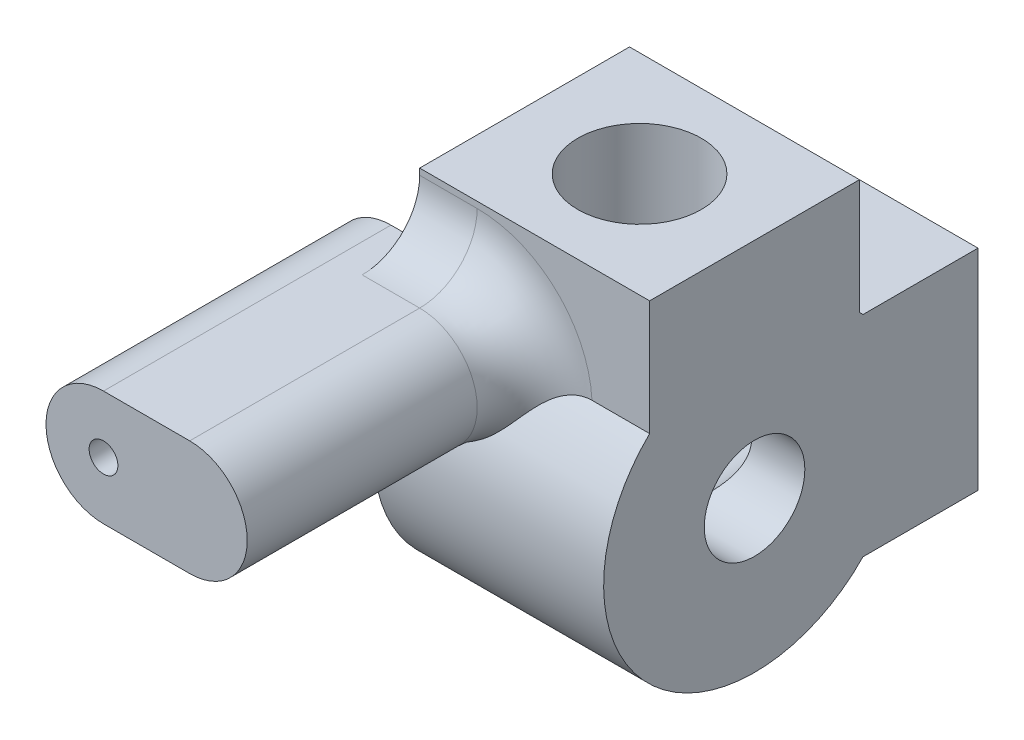
SolidWorks part; units mm, degrees
material "PLA Black"
ref_plane "Front" through (0, 0, 0) normal (0, 0, 1) x (1, 0, 0)
ref_plane "Top" through (0, 0, 0) normal (0, 1, 0) x (1, 0, 0)
ref_plane "Right" through (0, 0, 0) normal (1, 0, 0) x (0, 0, -1)
sketch "Sketch1" plane through (0, 0, 0) normal (1, 0, 0) x (0, 0, -1)
  line L0 (1.118, 1) -> (-1.118, 1) construction
  line L1 (-3.65, 3.7736) -> (3.65, 3.7736)
  line L2 (3.7736, 3.65) -> (3.7736, -3.65)
  line L3 (0, 0) -> (11.6334, 0) construction
  line L4 (0, 0) -> (0, 8.6732) construction
  arc A0 (-1.118, 1) -> (1.118, 1) centre (0, 0) ccw construction
  circle A1 centre (0, 0) radius 1.75
  arc A2 (3.7736, -3.65) -> (-3.65, 3.7736) centre (0, 0) cw
  arc A3 (3.7736, 3.65) -> (3.65, 3.7736) centre (0, 0) ccw
  dimension "D1" = 3
  dimension "D3" = 0.25
  dimension "D5" = 3.5
  dimension "D2" = 1
  dimension "D4" = 7.3
extrude "Boss-Extrude1" add sketch "Sketch1" along normal mid plane 8
sketch "Sketch2" plane through (0, 3.7736, 0) normal (0, 1, 0) x (1, 0, 0)
  circle A0 centre (0, 0) radius 2.15
  dimension "D1" = 4.3
extrude "Cut-Extrude1" cut sketch "Sketch2" against normal blind 5
sketch "Sketch3" plane through (0, 0, -3.7736) normal (0, 0, -1) x (-1, 0, 0)
  circle A0 centre (0, 0) radius 2.15
  dimension "D1" = 4.3
extrude "Cut-Extrude2" cut sketch "Sketch3" against normal blind 5
sketch "Sketch4" plane through (0, 3.7736, 0) normal (0, 1, 0) x (1, 0, 0)
  line L0 (4, 3.65) -> (-4, 3.65) construction
  line L1 (4, 3.65) -> (4, -3.65) construction
  line L2 (4, -3.65) -> (-4, -3.65) construction
  line L3 (-4, 3.65) -> (-4, -3.65) construction
  line L4 (4, 3.65) -> (-4, 3.65)
  line L5 (4, 3.65) -> (4, -3.65)
  line L6 (4, -3.65) -> (-4, -3.65)
  line L7 (-4, 3.65) -> (-4, -3.65)
  circle A0 centre (0, 0) radius 2.15 construction
  circle A1 centre (0, 0) radius 2.15
extrude "Boss-Extrude2" add sketch "Sketch4" along normal blind 4
sketch "Sketch5" plane through (0, 0, -3.7736) normal (0, 0, -1) x (-1, 0, 0)
  line L0 (-4, 3.65) -> (4, 3.65) construction
  line L1 (4, -3.65) -> (4, 3.65) construction
  line L2 (-4, -3.65) -> (4, -3.65) construction
  line L3 (-4, -3.65) -> (-4, 3.65) construction
  line L4 (-4, 3.65) -> (4, 3.65)
  line L5 (4, -3.65) -> (4, 3.65)
  line L6 (-4, -3.65) -> (4, -3.65)
  line L7 (-4, -3.65) -> (-4, 3.65)
  circle A0 centre (0, 0) radius 2.15 construction
  circle A1 centre (0, 0) radius 2.15
extrude "Boss-Extrude3" add sketch "Sketch5" along normal blind 4
ref_axis "Axis1" through (4, 0, 0) along (-1, 0, 0)
sketch "Sketch6" plane through (0, 0, 3.65) normal (0, 0, 1) x (1, 0, 0)
  line L0 (-4, 7.7736) -> (-4, 3.7736) construction
  line L2 (-2, 5.555) -> (-5, 5.555)
  line L3 (-5, 1.555) -> (-2, 1.555)
  line L6 (4, 0) -> (-4, 0) construction
  circle A0 centre (-5, 3.555) radius 0.5
  arc A1 (-5, 5.555) -> (-5, 1.555) centre (-5, 3.555) ccw
  arc A2 (-2, 5.555) -> (-2, 1.555) centre (-2, 3.555) cw
  dimension "D1" = 1
  dimension "D2" = 3.555
  dimension "D3" = 1.5
  dimension "D4" = 1
  dimension "D5" = 3
extrude "Boss-Extrude4" add sketch "Sketch6" along normal blind 10
fillet "Fillet1" radius 2 2 edges at (-0.6653, 5.0445, 3.65) (-3, 5.555, 3.65)
equation "\"knee_angle\"= 70"
equation "\"ankle_angle\" = 120"
equation "\"hip_angle\" = 30"
equation "\"spring_ankle_parallel_arm_diameter\"= 0.89"
equation "\"spring_ankle_parallel_arm_length\"= 13"
equation "\"spring_ankle_parallel_intern_diameter\"= 6.22"
equation "\"spring_ankle_parallel_angle\"= \"ankle_angle\""
equation "\"spring_ankle_parallel_turns\"= 3"
equation "\"spring_ankle_parallel_pitch\"= \"spring_ankle_parallel_arm_diameter\" * 1.01"
equation "\"spring_ankle_parallel_cutting_distance\"= (1-\"spring_ankle_parallel_angle\" / 360) * \"spring_ankle_parallel_pitch\""
equation "\"spring_ankle_serial_arm_diameter\"= 0.89"
equation "\"spring_ankle_serial_arm_length\"= 10"
equation "\"spring_ankle_serial_intern_diameter\"= 6.22"
equation "\"spring_ankle_serial_angle\"= \"90\""
equation "\"spring_ankle_serial_turns\"= 3"
equation "\"spring_ankle_serial_pitch\"= \"spring_ankle_serial_arm_diameter\" * 1.01"
equation "\"spring_ankle_serial_cutting_distance\"= (1-\"spring_ankle_serial_angle\" / 360) * \"spring_ankle_serial_pitch\""
equation "\"spring_knee_parallel_arm_diameter\"= 0.43"
equation "\"spring_knee_parallel_arm_length\"= 15"
equation "\"spring_knee_parallel_intern_diameter\"= 5.46"
equation "\"spring_knee_parallel_angle\"= \"knee_angle\""
equation "\"spring_knee_parallel_turns\"= 3"
equation "\"spring_knee_parallel_pitch\"= \"spring_knee_parallel_arm_diameter\" * 1.01"
equation "\"spring_knee_parallel_cutting_distance\"= (1-\"spring_knee_parallel_angle\" / 360) * \"spring_knee_parallel_pitch\""
equation "\"spring_knee_serial_arm_diameter\"= 0.43"
equation "\"spring_knee_serial_arm_length\"= 10"
equation "\"spring_knee_serial_intern_diameter\"= 5.46"
equation "\"spring_knee_serial_angle\"= \"90\""
equation "\"spring_knee_serial_turns\"= 3"
equation "\"spring_knee_serial_pitch\"= \"spring_knee_serial_arm_diameter\" * 1.01"
equation "\"spring_knee_serial_cutting_distance\"= (1-\"spring_knee_serial_angle\" / 360) * \"spring_knee_serial_pitch\""
equation "\"D2@Sketch6\"=(\"spring_ankle_serial_intern_diameter\" + \"spring_ankle_serial_arm_diameter\")/2"
